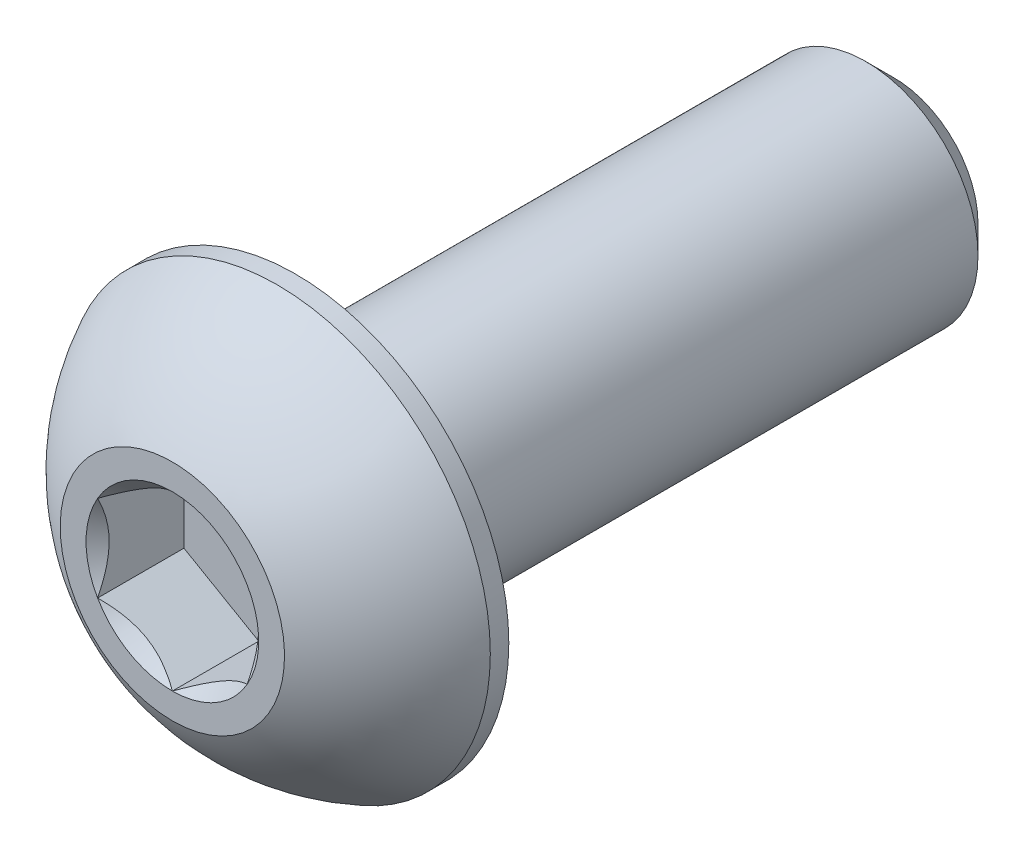
SolidWorks part; units mm, degrees
ref_plane "Front" through (0, 0, 0) normal (0, 0, 1) x (1, 0, 0)
ref_plane "Top" through (0, 0, 0) normal (0, 1, 0) x (1, 0, 0)
ref_plane "Right" through (0, 0, 0) normal (1, 0, 0) x (0, 0, -1)
sketch "Sketch1" plane through (0, 0, 0) normal (1, 0, 0) x (0, 0, -1)
  line L2 (1.65, 1.5) -> (9.65, 1.5)
  line L3 (9.65, 1.5) -> (9.65, 0)
  line L4 (9.65, 0) -> (1.65, 0)
  line L6 (1.4025, 2.85) -> (1.65, 2.85) construction
  line L7 (9.65, 1.5) -> (9.65, -1.5) construction
  line L8 (0, 0) -> (1.65, 0) construction
  line L9 (1.65, 2.85) -> (1.65, -2.85) construction
  line L11 (1.65, 1.5) -> (1.65, 0)
  line L13 (0, 1) -> (0, -1) construction
  line L14 (0, 1) -> (0, 1.5) construction
  line L15 (9.6187, 1.5541) -> (9.8687, 1.1211) construction
  line L16 (9.8687, 1.1211) -> (10.1187, 1.5541) construction
  line L17 (10.1187, 1.5541) -> (9.6187, 1.5541) construction
  line L18 (9.65, 1.5) -> (10.0875, 1.5) construction
  line L19 (9.8687, 1.5541) -> (9.8687, 1.5) construction
  line L20 (9.8687, 1.5) -> (9.8687, 1.1752) construction
  line L21 (9.8687, 1.1752) -> (9.8687, 1.1211) construction
  line L22 (9.8375, 1.1752) -> (9.9, 1.1752)
  line L23 (9.6344, 1.5271) -> (10.1031, 1.5271)
  line L24 (9.9, 1.1752) -> (10.1031, 1.5271)
  line L25 (9.8375, 1.1752) -> (9.6344, 1.5271)
  line L26 (9.275, 1.5) -> (9.65, 1.125)
  arc A3 (0, 1.5) -> (1.4025, 2.85) centre (2.7948, 0) cw construction
  point P29 (9.8687, 1.5271)
  point P30 (8.4, -1.5)
  dimension "D1" = 0.2475
  dimension "Pitch" = 0.5
  dimension "D3" = 0.0625
  dimension "D2" = 0.375
  dimension "D4" = 45
  dimension "D5" = 1.25
sketch "Sketch10" plane through (0, 0, 0) normal (1, 0, 0) x (0, 0, -1)
  line L0 (9.275, 1.5) -> (9.65, 1.125) construction
  line L1 (9.275, 1.5) -> (9.65, 1.125)
  line L4 (9.65, 1.5) -> (1.65, 1.5)
  line L5 (9.65, 0) -> (9.65, 1.5)
  line L6 (1.65, 0) -> (9.65, 0)
  line L7 (1.65, 1.5) -> (1.65, 0)
  line L8 (9.275, 1.5) -> (1.65, 1.5)
  line L9 (9.65, 0) -> (9.65, 1.125)
  line L10 (1.65, 0) -> (9.65, 0)
  line L11 (1.65, 1.5) -> (1.65, 0)
  dimension "D1" = 0
revolve "Revolve3" add sketch "Sketch10" angle 360 about L8
sketch "Sketch7" plane through (0, 0, 0) normal (1, 0, 0) x (0, 0, -1)
  line L6 (1.4025, 2.85) -> (1.65, 2.85) construction
  line L8 (0, 0) -> (1.65, 0) construction
  line L11 (1.65, 2.85) -> (1.65, -2.85) construction
  line L12 (1.4025, 2.85) -> (1.65, 2.85)
  line L13 (0, 0) -> (1.65, 0)
  line L14 (0, 1) -> (0, -1) construction
  line L15 (1.65, 2.85) -> (1.65, 0)
  line L16 (0, 1.5) -> (0, 0)
  arc A2 (1.4025, 2.85) -> (0, 1.5) centre (2.7948, 0) ccw construction
  arc A3 (1.4025, 2.85) -> (0, 1.5) centre (2.7948, 0) ccw
revolve "Revolve2" add sketch "Sketch7" angle 360 mid plane about L13
sketch "Sketch5" plane through (0, 0, 0) normal (0, 0, 1) x (1, 0, 0)
  line L1 (1, -0.5774) -> (1, 0.5774)
  line L2 (1, 0.5774) -> (0, 1.1547)
  line L3 (0, 1.1547) -> (-1, 0.5774)
  line L4 (-1, 0.5774) -> (-1, -0.5774)
  line L5 (-1, -0.5774) -> (0, -1.1547)
  line L6 (0, -1.1547) -> (1, -0.5774)
  circle A0 centre (0, 0) radius 1 construction
extrude "Cut-Extrude2" cut sketch "Sketch5" against normal blind 1.155
sketch "Sketch6" plane through (0, 0, 0) normal (0, 0, 1) x (1, 0, 0)
  circle A0 centre (0, 0) radius 1.1547
extrude "Cut-Extrude3" cut sketch "Sketch6" against normal blind 1.155 draft 45
sketch "Sketch9" [suppressed] plane through (0, 0, -1.65) normal (0, 0, -1) x (-1, 0, 0)
  circle A0 centre (0, 0) radius 1.5 construction
  circle A4 centre (0, 0) radius 1.5
split "Split1" [suppressed] bodies to split 113
sketch "Sketch11" [suppressed] plane through (0, 0, -9.65) normal (0, 0, -1) x (-1, 0, 0)
  circle A0 centre (0, 0) radius 1.5 construction
  circle A1 centre (0, 0) radius 1.5
curve "Helix/Spiral1" [suppressed] pitch 0.5 height 9.65 turns 19.3
sketch "Sketch12" [suppressed] plane through (0, 0, 0) normal (1, 0, 0) x (0, 0, -1)
  line L0 (9.8375, 1.1752) -> (9.9, 1.1752) construction
  line L1 (9.9, 1.1752) -> (10.1031, 1.5271) construction
  line L2 (9.6344, 1.5271) -> (10.1031, 1.5271) construction
  line L3 (9.8375, 1.1752) -> (9.6344, 1.5271) construction
  line L4 (9.8375, 1.1752) -> (9.9, 1.1752)
  line L5 (9.9, 1.1752) -> (10.1031, 1.5271)
  line L6 (9.6344, 1.5271) -> (10.1031, 1.5271)
  line L7 (9.8375, 1.1752) -> (9.6344, 1.5271)
sweep "Cut-Sweep2" [suppressed] cut profiles "Sketch12" path "Helix/Spiral1"
extrude "Boss-Extrude1" [suppressed] add sketch "Sketch9" along normal blind 10 draft 45
equation "\"D1@Cut-Extrude2\" = \"Head Ht@Sketch1\" * .7"
equation "\"D1@Sketch1\" = \"Head Ht@Sketch1\" * .15"
equation "\"D1@Cut-Extrude3\" = \"D1@Cut-Extrude2\""
equation "\"D3@Sketch1\" = \"Pitch@Sketch1\" / 8"
equation "\"D2@Sketch1\"=\"Pitch@Sketch1\"*0.75"
equation "\"D3@Helix/Spiral1\" = \"Lg@Sketch1\" + \"Head Ht@Sketch1\""
equation "\"D4@Helix/Spiral1\"=\"pitch@sketch1\""
equation "\"D5@Sketch1\"=\"Pitch@Sketch1\"*2.5"
